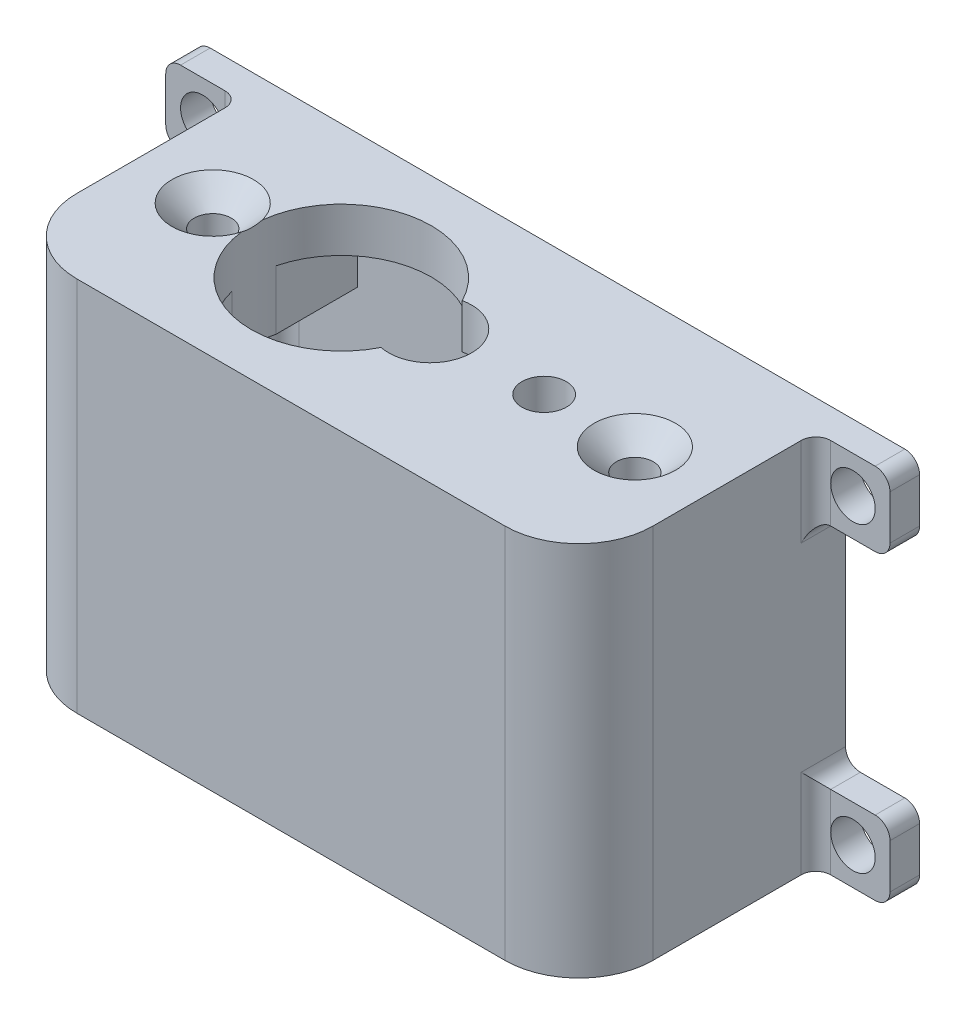
SolidWorks part; units mm, degrees
ref_plane "Спереди" through (0, 0, 0) normal (0, 0, 1) x (1, 0, 0)
ref_plane "Сверху" through (0, 0, 0) normal (0, 1, 0) x (1, 0, 0)
ref_plane "Справа" through (0, 0, 0) normal (1, 0, 0) x (0, 0, -1)
sketch "Эскиз1" plane through (0, 0, 0) normal (0, 0, 1) x (1, 0, 0)
  line L16 (11.4979, 22.2) -> (11.4979, 18.2)
  line L17 (11.4979, 18.2) -> (16.4979, 18.2)
  line L18 (16.4979, 15.8) -> (16.4979, 18.2)
  line L24 (-16.4021, 18.2) -> (-16.4021, 15.8)
  line L25 (-16.4021, 18.2) -> (-11.4417, 18.2)
  line L26 (-11.4417, 22.2) -> (-11.4417, 18.2)
  line L28 (-19.4021, -0.2) -> (-19.4021, 25.2)
  line L30 (-16.4021, 15.8) -> (-16.4021, -0.2)
  line L36 (16.4979, -0.2) -> (16.4979, 15.8)
  line L41 (-19.4021, 25.2) -> (19.4979, 25.2)
  line L42 (19.4979, -0.2) -> (19.4979, 25.2)
  line L43 (-11.4417, 22.2) -> (11.4979, 22.2)
  line L44 (-19.4021, -0.2) -> (-16.4021, -0.2)
  line L45 (16.4979, -0.2) -> (19.4979, -0.2)
extrude "Бобышка-Вытянуть1" add sketch "Эскиз1" along normal mid plane 14
sketch "Эскиз3" plane through (0, 25.2, 0) normal (0, 1, 0) x (1, 0, 0)
  arc A2 (-0.1236, 2.7406) -> (-0.1236, -2.7406) centre (-5.55, 0) ccw
  arc A3 (-0.1236, -2.7406) -> (-0.1236, 2.7406) centre (0.45, 0) ccw
extrude "Вырез-Вытянуть1" cut sketch "Эскиз3" against normal through all
sketch "Эскиз4" plane through (0, 18.2, 0) normal (0, -1, 0) x (1, 0, 0)
  circle A0 centre (-14.2501, -0.021) radius 1.25
  circle A1 centre (14.2501, -0.021) radius 1.25
  dimension "D1" = 2.5
  dimension "D2" = 2.5
extrude "Вырез-Вытянуть2" cut sketch "Эскиз4" against normal through all
sketch "Эскиз5" plane through (0, 0, -7) normal (0, 0, -1) x (-1, 0, 0)
  line L0 (-0.0479, 25.2) -> (-0.0479, 15.8158) construction
  line L1 (-19.4979, 25.2) -> (19.4021, 25.2)
  line L2 (-19.4979, 19.2) -> (-19.4979, 5.8)
  line L4 (19.4021, 19.2) -> (19.4021, 5.8)
  line L5 (-19.4979, 25.2) -> (-23.4979, 25.2)
  line L7 (-20.4979, 20.2) -> (-23.4979, 20.2)
  line L8 (-24.4979, 24.2) -> (-24.4979, 21.2)
  line L9 (-19.4979, 9.5) -> (26.1292, 9.5) construction
  line L10 (-24.4979, 25.2) -> (-19.4979, 20.2) construction
  line L11 (19.4021, 12.5) -> (-26.4645, 12.5) construction
  line L12 (-24.4979, -0.2) -> (-19.4979, 4.8) construction
  line L13 (-24.4979, 0.8) -> (-24.4979, 3.8)
  line L14 (-20.4979, 4.8) -> (-23.4979, 4.8)
  line L15 (23.4021, -0.2) -> (-23.4979, -0.2)
  line L16 (24.4021, -0.2) -> (19.4021, 4.8) construction
  line L17 (-19.4979, 12.5) -> (26.3686, 12.5) construction
  line L18 (24.4021, 25.2) -> (19.4021, 20.2) construction
  line L19 (-19.4979, -0.2) -> (23.4021, -0.2)
  line L20 (20.4021, 4.8) -> (23.4021, 4.8)
  line L21 (24.4021, 0.8) -> (24.4021, 3.8)
  line L22 (24.4021, 24.2) -> (24.4021, 21.2)
  line L23 (20.4021, 20.2) -> (23.4021, 20.2)
  line L24 (19.4021, 25.2) -> (23.4021, 25.2)
  circle A0 centre (-21.9979, 22.7) radius 1.5
  arc A1 (-19.4979, 19.2) -> (-20.4979, 20.2) centre (-20.4979, 19.2) ccw
  arc A2 (-23.4979, 20.2) -> (-24.4979, 21.2) centre (-23.4979, 21.2) cw
  arc A3 (-23.4979, 25.2) -> (-24.4979, 24.2) centre (-23.4979, 24.2) ccw
  arc A4 (-23.4979, -0.2) -> (-24.4979, 0.8) centre (-23.4979, 0.8) cw
  arc A5 (-23.4979, 4.8) -> (-24.4979, 3.8) centre (-23.4979, 3.8) ccw
  arc A6 (-19.4979, 5.8) -> (-20.4979, 4.8) centre (-20.4979, 5.8) cw
  circle A7 centre (-21.9979, 2.3) radius 1.5
  circle A8 centre (21.9021, 2.3) radius 1.5
  arc A9 (19.4021, 5.8) -> (20.4021, 4.8) centre (20.4021, 5.8) ccw
  arc A10 (23.4021, 4.8) -> (24.4021, 3.8) centre (23.4021, 3.8) cw
  arc A11 (23.4021, -0.2) -> (24.4021, 0.8) centre (23.4021, 0.8) ccw
  arc A12 (23.4021, 25.2) -> (24.4021, 24.2) centre (23.4021, 24.2) cw
  arc A13 (23.4021, 20.2) -> (24.4021, 21.2) centre (23.4021, 21.2) ccw
  arc A14 (19.4021, 19.2) -> (20.4021, 20.2) centre (20.4021, 19.2) cw
  circle A15 centre (21.9021, 22.7) radius 1.5
  point P20 (-24.4979, 20.2)
  point P39 (-24.4979, 4.8)
  point P68 (24.4021, 4.8)
  point P69 (24.4021, 20.2)
  line M33 (16.4021, -0.2) -> (19.4021, -0.2)
  line M34 (19.4021, -0.2) -> (19.4021, 25.2)
  line M35 (19.4021, 25.2) -> (-19.4979, 25.2)
  line M36 (-19.4979, 25.2) -> (-19.4979, -0.2)
  line M37 (-19.4979, -0.2) -> (-16.4979, -0.2)
  line M38 (-16.4979, -0.2) -> (-16.4979, 18.2)
  line M39 (-16.4979, 18.2) -> (-11.4979, 18.2)
  line M40 (-11.4979, 18.2) -> (-11.4979, 22.2)
  line M41 (-11.4979, 22.2) -> (11.4417, 22.2)
  line M42 (11.4417, 22.2) -> (11.4417, 18.2)
  line M43 (11.4417, 18.2) -> (16.4021, 18.2)
  line M44 (16.4021, 18.2) -> (16.4021, -0.2)
  dimension "D1" = 1
  dimension "D2" = 5
extrude "Бобышка-Вытянуть2" add sketch "Эскиз5" along normal blind 2 contours M44 M33 M34 M35 M36 M37 M38 M39 M40 M41 M42 M43 | A14 L23 A13 L22 A12 L24 A15 M34 | L15 A11 L21 A10 L20 A9 A8 M34 | L15 M44 M43 M42 M41 M40 M39 M38 | A6 L14 A5 L13 A4 L15 A7 M36 | L5 A3 L8 A2 L7 A1 A0 M36 region at (19.576, 22.2, -7) region at (0.0479, 24.7354, -7) region at (-21.4021, 25.1219, -7) region at (19.576, 2.8, -7) region at (-19.6397, 5.0377, -7) region at (0.0453, 10.4742, -7)
sketch "Эскиз6" plane through (0, 0, 7) normal (0, 0, 1) x (1, 0, 0)
  line L0 (-19.4021, 25.2) -> (-19.4021, -0.2) construction
  line L1 (19.4979, 25.2) -> (-19.4021, 25.2)
  line L2 (19.4979, 25.2) -> (19.4979, -0.2)
  line L3 (19.4979, -0.2) -> (-19.4021, -0.2)
  line L4 (-19.4021, 25.2) -> (-19.4021, -0.2)
extrude "Бобышка-Вытянуть3" add sketch "Эскиз6" along normal blind 2
fillet "Скругление1" radius 1 4 edges at (-19.4021, 2.8, -7) (-19.4021, 22.2, -7) (19.4979, 22.2, -7) (19.4979, 2.8, -7)
sketch "Эскиз7" plane through (0, 0, -7) normal (0, 0, 1) x (1, 0, 0)
  line L1 (-7.7522, 4.1406) -> (-15.7522, 4.1406)
  line L2 (-7.7522, 4.1406) -> (-7.7522, 7.1406)
  line L3 (-7.7522, 7.1406) -> (-15.7522, 7.1406)
  line L4 (-15.7522, 4.1406) -> (-15.7522, 7.1406)
  dimension "D1" = 8
  dimension "D2" = 3
extrude "Вырез-Вытянуть3" cut sketch "Эскиз7" against normal through all
fillet "Скругление2" radius 1 5 edges at (16.4979, 9, -7) (-7.7522, 4.1406, -8) (-7.7522, 7.1406, -8) (-15.7522, 4.1406, -8) (-15.7522, 7.1406, -8)
fillet "Скругление3" radius 1 3 edges at (16.4979, 9, 7) (-16.4021, 9, 7) (-16.4021, 9, -7)
fillet "Скругление5" radius 5 2 edges at (19.4979, 12.5, 9) (-19.4021, 12.5, 9)
sketch "Sketch1" plane through (0, 25.2, 0) normal (0, 1, 0) x (1, 0, 0)
  line L1 (3.2499, 0.021) -> (13.0001, 0.021) construction
  circle A2 centre (8.125, 0.021) radius 1.5
  dimension "D1" = 3
extrude "Cut-Extrude1" cut sketch "Sketch1" against normal blind 10
chamfer "Chamfer1" distance 1.5 angle 45 2 edges at (14.2501, 25.2, -1.271) (-14.2501, 25.2, -1.271)
sketch "Sketch2" plane through (0, 22.2, 0) normal (0, -1, 0) x (1, 0, 0)
  line L0 (15.4979, -7) -> (-15.4021, -7) construction
  line L1 (11.4979, 7) -> (4.755, 7)
  line L2 (11.4979, 7) -> (11.4979, -7)
  line L3 (11.4979, -7) -> (4.755, -7)
  line L4 (4.755, 7) -> (4.755, -7)
  line L5 (11.4979, -7) -> (4.755, -7) construction
  circle A0 centre (8.125, -0.021) radius 1.55
extrude "Boss-Extrude1" add sketch "Sketch2" along normal offset from surface (2 mm away) 2 up to face at (14.2501, 18.2, -1.271)
sketch "Sketch3" plane through (0, 20.2, 0) normal (0, -1, 0) x (1, 0, 0)
  circle A0 centre (8.125, -0.021) radius 3
  dimension "D1" = 6
extrude "Cut-Extrude2" cut sketch "Sketch3" against normal up to surface (2 mm away) up to face at (-4.2489, 22.2, 0)
